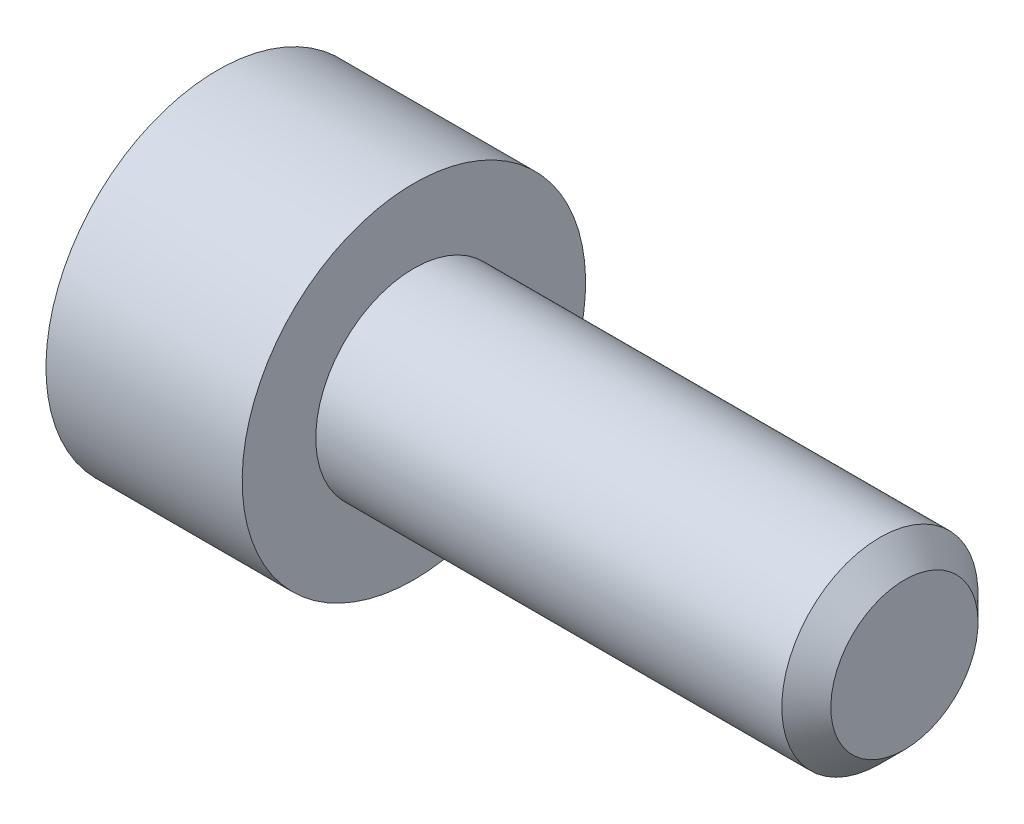
SolidWorks part; units mm, degrees
material "市購件"
ref_plane "前基準面" through (0, 0, 0) normal (0, 0, 1) x (1, 0, 0)
ref_plane "上基準面" through (0, 0, 0) normal (0, 1, 0) x (1, 0, 0)
ref_plane "右基準面" through (0, 0, 0) normal (1, 0, 0) x (0, 0, -1)
sketch "草圖1" plane through (0, 0, 0) normal (0, 0, 1) x (1, 0, 0)
  line L0 (-4, 0) -> (-4, 3.5)
  line L1 (-4, 3.5) -> (0, 3.5)
  line L2 (0, 3.5) -> (0, 2)
  line L3 (0, 2) -> (9.5, 2)
  line L4 (9.5, 2) -> (10, 1.5)
  line L5 (10, 1.5) -> (10, 0)
  line L6 (10, 0) -> (-4, 0)
  line L7 (10, 0) -> (-4, 0) construction
  dimension "D1" = 0.5
  dimension "D2" = 0.5
  dimension "D3" = 10
revolve "旋轉1" add sketch "草圖1" angle 360 about L7 reverse direction yes
cosmetic thread "裝飾螺紋線1"
sketch "草圖2" plane through (0, 0, 0) normal (0, 0, 1) x (1, 0, 0)
  line L0 (-4, 0) -> (-4, 1.5)
  line L1 (-4, 1.5) -> (-2, 1.5)
  line L2 (-2, 1.5) -> (-1.5981, 0)
  line L3 (-1.5981, 0) -> (-4, 0)
  line L4 (-1.5981, 0) -> (-4, 0) construction
revolve "除料-旋轉1" cut sketch "草圖2" angle 360 about L4 reverse direction yes
ref_plane "平面1" through (-4, 0, 0) normal (1, 0, 0) x (0, 0, -1)
sketch "草圖3" plane through (-4, 0, 0) normal (1, 0, 0) x (0, 0, -1)
  line L0 (-1.5, 0.866) -> (-1.5, -0.866)
  line L1 (-1.5, -0.866) -> (0, -1.7321)
  line L2 (0, -1.7321) -> (1.5, -0.866)
  line L3 (1.5, -0.866) -> (1.5, 0.866)
  line L4 (1.5, 0.866) -> (0, 1.7321)
  line L5 (0, 1.7321) -> (-1.5, 0.866)
extrude "除料-伸長1" cut sketch "草圖3" along normal blind 2
ref_plane "平面2" through (16, 0, 0) normal (1, 0, 0) x (0, 0, -1)
ref_plane "screw1 XY" through (0, 0, 0) normal (1, 0, 0) x (0, 0, -1)
ref_plane "screw1 XZ" through (0, 0, 0) normal (0, -1, 0) x (-1, 0, 0)
ref_plane "screw1 YZ" through (0, 0, 0) normal (0, 0, -1) x (-1, 0, 0)
ref_axis "screw1 X" through (0, 0, 80.9) along (0, 0, -1)
ref_axis "screw1 Y" through (0, -50, 0) along (0, 1, 0)
ref_axis "screw1 Z" through (80.9, 0, 0) along (-1, 0, 0)
sketch3d "screw1"
  point P0 (0, 0, 0)
ref_plane "bolt_to_nut XY" through (16, 0, 0) normal (1, 0, 0) x (0, 0, -1)
ref_plane "bolt_to_nut XZ" through (0, 0, 0) normal (0, -1, 0) x (-1, 0, 0)
ref_plane "bolt_to_nut YZ" through (0, 0, 0) normal (0, 0, -1) x (-1, 0, 0)
ref_axis "bolt_to_nut X" through (16, 0, 80.9) along (0, 0, -1)
ref_axis "bolt_to_nut Y" through (16, -50, 0) along (0, 1, 0)
ref_axis "bolt_to_nut Z" through (80.9, 0, 0) along (-1, 0, 0)
sketch3d "bolt_to_nut"
  point P0 (16, 0, 0)
